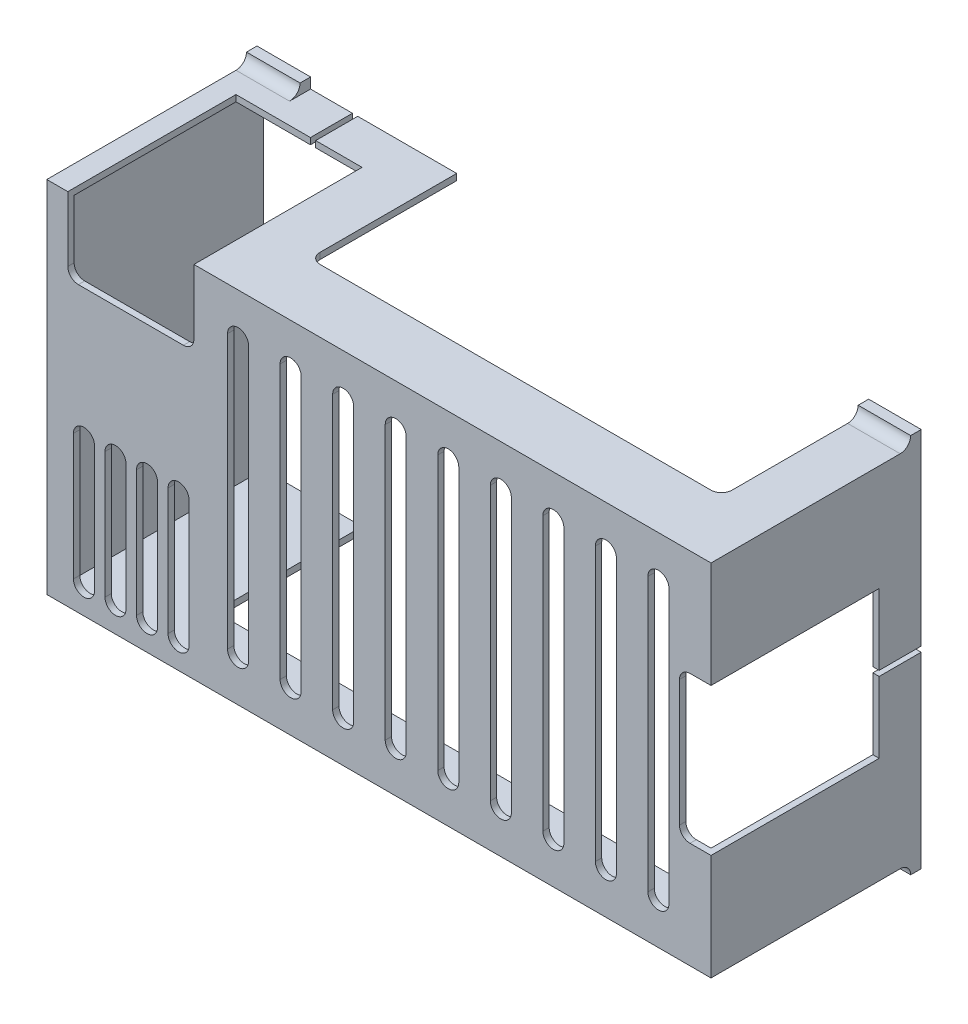
SolidWorks part; units mm, degrees
ref_plane "Front" through (0, 0, 0) normal (0, 0, 1) x (1, 0, 0)
ref_plane "Top" through (0, 0, 0) normal (0, 1, 0) x (1, 0, 0)
ref_plane "Right" through (0, 0, 0) normal (1, 0, 0) x (0, 0, -1)
sketch "Эскиз1" plane through (0, 0, 0) normal (0, 0, 1) x (1, 0, 0)
  line L1 (-62, 33) -> (62, 33)
  line L2 (-62, 33) -> (-62, -33)
  line L3 (-62, -33) -> (62, -33)
  line L4 (62, 33) -> (62, -33)
  line L5 (-62, 33) -> (62, -33) construction
  line L6 (-62, -33) -> (62, 33) construction
  point P0 (0, 0)
  dimension "D1" = 124
  dimension "D2" = 66
extrude "Вытянуть-Тонкостенный1" add sketch "Эскиз1" along normal blind 40 thin thin type one direction wall 1.2
sketch "Эскиз2" plane through (0, 0, 40) normal (0, 0, 1) x (1, 0, 0)
  line L1 (-63.2, 34.2) -> (63.2, 34.2)
  line L2 (-63.2, 34.2) -> (-63.2, -34.2)
  line L3 (-63.2, -34.2) -> (63.2, -34.2)
  line L4 (63.2, 34.2) -> (63.2, -34.2)
extrude "Бобышка-Вытянуть1" add sketch "Эскиз2" against normal blind 1.2
sketch "Эскиз3" plane through (0, 0, 40) normal (0, 0, 1) x (1, 0, 0)
  line L0 (63.2, -34.2) -> (63.2, 34.2) construction
  line L1 (59.2, -14) -> (69.2, -14)
  line L2 (57.2, -12) -> (57.2, 12)
  line L3 (59.2, 14) -> (69.2, 14)
  line L4 (69.2, -14) -> (69.2, 14)
  line L5 (57.2, -14) -> (69.2, 14) construction
  line L6 (57.2, 14) -> (69.2, -14) construction
  arc A0 (59.2, -14) -> (57.2, -12) centre (59.2, -12) cw
  arc A1 (57.2, 12) -> (59.2, 14) centre (59.2, 12) cw
  point P0 (63.2, 0)
  dimension "D3" = 2
  dimension "D1" = 12
  dimension "D2" = 28
extrude "Вырез-Вытянуть1" cut sketch "Эскиз3" against normal blind 32
sketch "Эскиз4" plane through (0, 0, 40) normal (0, 0, 1) x (1, 0, 0)
  line L0 (57.2, 0) -> (-63.2, 0) construction
  line L1 (57.2, 12) -> (57.2, -12) construction
  line L2 (-63.2, 34.2) -> (-63.2, -34.2) construction
  line L3 (53.2, -26) -> (53.2, 26) construction
  line L4 (51.2, -26) -> (51.2, 26)
  line L5 (55.2, -26) -> (55.2, 26)
  line L6 (63.2, 14) -> (63.2, -14) construction
  line L7 (43.2, -26) -> (43.2, 26) construction
  line L8 (41.2, -26) -> (41.2, 26)
  line L9 (45.2, -26) -> (45.2, 26)
  line L10 (33.2, -26) -> (33.2, 26) construction
  line L11 (31.2, -26) -> (31.2, 26)
  line L12 (35.2, -26) -> (35.2, 26)
  line L13 (23.2, -26) -> (23.2, 26) construction
  line L14 (21.2, -26) -> (21.2, 26)
  line L15 (25.2, -26) -> (25.2, 26)
  line L16 (13.2, -26) -> (13.2, 26) construction
  line L17 (11.2, -26) -> (11.2, 26)
  line L18 (15.2, -26) -> (15.2, 26)
  line L19 (3.2, -26) -> (3.2, 26) construction
  line L20 (1.2, -26) -> (1.2, 26)
  line L21 (5.2, -26) -> (5.2, 26)
  line L22 (-6.8, -26) -> (-6.8, 26) construction
  line L23 (-8.8, -26) -> (-8.8, 26)
  line L24 (-4.8, -26) -> (-4.8, 26)
  line L25 (-16.8, -26) -> (-16.8, 26) construction
  line L26 (-18.8, -26) -> (-18.8, 26)
  line L27 (-14.8, -26) -> (-14.8, 26)
  line L28 (-26.8, -26) -> (-26.8, 26) construction
  line L29 (-28.8, -26) -> (-28.8, 26)
  line L30 (-24.8, -26) -> (-24.8, 26)
  line L31 (-32.5505, 0) -> (-32.5505, -34.2) construction
  line L34 (-63.2, -34.2) -> (63.2, -34.2) construction
  line L35 (-32.5505, -17.1) -> (-63.2, -17.1) construction
  line L36 (-38.1278, -29.1) -> (-38.1278, -5.1) construction
  line L37 (-40.1278, -29.1) -> (-40.1278, -5.1)
  line L38 (-36.1278, -29.1) -> (-36.1278, -5.1)
  line L39 (-44.1278, -29.1) -> (-44.1278, -5.1) construction
  line L40 (-46.1278, -29.1) -> (-46.1278, -5.1)
  line L41 (-42.1278, -29.1) -> (-42.1278, -5.1)
  line L42 (-50.1278, -29.1) -> (-50.1278, -5.1) construction
  line L43 (-52.1278, -29.1) -> (-52.1278, -5.1)
  line L44 (-48.1278, -29.1) -> (-48.1278, -5.1)
  line L45 (-56.1278, -29.1) -> (-56.1278, -5.1) construction
  line L46 (-58.1278, -29.1) -> (-58.1278, -5.1)
  line L47 (-54.1278, -29.1) -> (-54.1278, -5.1)
  arc A0 (51.2, -26) -> (55.2, -26) centre (53.2, -26) ccw
  arc A1 (55.2, 26) -> (51.2, 26) centre (53.2, 26) ccw
  arc A2 (41.2, -26) -> (45.2, -26) centre (43.2, -26) ccw
  arc A3 (45.2, 26) -> (41.2, 26) centre (43.2, 26) ccw
  arc A4 (31.2, -26) -> (35.2, -26) centre (33.2, -26) ccw
  arc A5 (35.2, 26) -> (31.2, 26) centre (33.2, 26) ccw
  arc A6 (21.2, -26) -> (25.2, -26) centre (23.2, -26) ccw
  arc A7 (25.2, 26) -> (21.2, 26) centre (23.2, 26) ccw
  arc A8 (11.2, -26) -> (15.2, -26) centre (13.2, -26) ccw
  arc A9 (15.2, 26) -> (11.2, 26) centre (13.2, 26) ccw
  arc A10 (1.2, -26) -> (5.2, -26) centre (3.2, -26) ccw
  arc A11 (5.2, 26) -> (1.2, 26) centre (3.2, 26) ccw
  arc A12 (-8.8, -26) -> (-4.8, -26) centre (-6.8, -26) ccw
  arc A13 (-4.8, 26) -> (-8.8, 26) centre (-6.8, 26) ccw
  arc A14 (-18.8, -26) -> (-14.8, -26) centre (-16.8, -26) ccw
  arc A15 (-14.8, 26) -> (-18.8, 26) centre (-16.8, 26) ccw
  arc A16 (-28.8, -26) -> (-24.8, -26) centre (-26.8, -26) ccw
  arc A17 (-24.8, 26) -> (-28.8, 26) centre (-26.8, 26) ccw
  arc A20 (-40.1278, -29.1) -> (-36.1278, -29.1) centre (-38.1278, -29.1) ccw
  arc A21 (-36.1278, -5.1) -> (-40.1278, -5.1) centre (-38.1278, -5.1) ccw
  arc A22 (-46.1278, -29.1) -> (-42.1278, -29.1) centre (-44.1278, -29.1) ccw
  arc A23 (-42.1278, -5.1) -> (-46.1278, -5.1) centre (-44.1278, -5.1) ccw
  arc A24 (-52.1278, -29.1) -> (-48.1278, -29.1) centre (-50.1278, -29.1) ccw
  arc A25 (-48.1278, -5.1) -> (-52.1278, -5.1) centre (-50.1278, -5.1) ccw
  arc A26 (-58.1278, -29.1) -> (-54.1278, -29.1) centre (-56.1278, -29.1) ccw
  arc A27 (-54.1278, -5.1) -> (-58.1278, -5.1) centre (-56.1278, -5.1) ccw
  point P8 (53.2, 0)
  point P19 (43.2, 0)
  point P26 (33.2, 0)
  point P33 (23.2, 0)
  point P40 (13.2, 0)
  point P47 (3.2, 0)
  point P54 (-6.8, 0)
  point P61 (-16.8, 0)
  point P68 (-26.8, 0)
  point P79 (-38.1278, -17.1)
  point P88 (-44.1278, -17.1)
  point P95 (-50.1278, -17.1)
  point P102 (-56.1278, -17.1)
  dimension "D1" = 10
  dimension "D3" = 4
  dimension "D2" = 9
extrude "Вырез-Вытянуть2" cut sketch "Эскиз4" against normal up to next
sketch "Эскиз5" plane through (0, 0, 40) normal (0, 0, 1) x (1, 0, 0)
  line L0 (63.2, 34.2) -> (-63.2, 34.2) construction
  line L1 (-59.2, 48.5215) -> (-35.2, 48.5215)
  line L2 (-59.2, 48.5215) -> (-59.2, 21.8785)
  line L3 (-57.2, 19.8785) -> (-37.2, 19.8785)
  line L4 (-35.2, 48.5215) -> (-35.2, 21.8785)
  line L5 (-59.2, 48.5215) -> (-35.2, 19.8785) construction
  line L6 (-59.2, 19.8785) -> (-35.2, 48.5215) construction
  line L7 (-63.2, 34.2) -> (-63.2, -34.2) construction
  arc A0 (-37.2, 19.8785) -> (-35.2, 21.8785) centre (-37.2, 21.8785) ccw
  arc A1 (-59.2, 21.8785) -> (-57.2, 19.8785) centre (-57.2, 21.8785) ccw
  point P0 (-47.2, 34.2)
  dimension "D3" = 2
  dimension "D1" = 24
  dimension "D2" = 4
extrude "Вырез-Вытянуть3" cut sketch "Эскиз5" against normal blind 32
sketch "Эскиз6" plane through (0, -34.2, 0) normal (0, -1, 0) x (1, 0, 0)
  line L0 (-63.2, 0) -> (63.2, 0) construction
  line L1 (53.2, 0) -> (-43.2, 0)
  line L2 (53.2, 0) -> (53.2, 26)
  line L3 (51.2, 28) -> (-41.2, 28)
  line L4 (-43.2, 0) -> (-43.2, 26)
  line L5 (63.2, 40) -> (63.2, 0) construction
  line L6 (-63.2, 40) -> (-63.2, 0) construction
  arc A0 (53.2, 26) -> (51.2, 28) centre (51.2, 26) ccw
  arc A1 (-41.2, 28) -> (-43.2, 26) centre (-41.2, 26) ccw
  point P10 (-43.2, 28)
  dimension "D2" = 2
  dimension "D1" = 28
  dimension "D3" = 10
  dimension "D4" = 20
extrude "Вырез-Вытянуть4" cut sketch "Эскиз6" against normal up to next
sketch "Эскиз7" plane through (0, 34.2, 0) normal (0, 1, 0) x (1, 0, 0)
  line L0 (63.2, 0) -> (-63.2, 0) construction
  line L1 (53.2, 0) -> (-25.2, 0)
  line L2 (53.2, 0) -> (53.2, -26)
  line L3 (51.2, -28) -> (-23.2, -28)
  line L4 (-25.2, 0) -> (-25.2, -26)
  line L5 (63.2, -40) -> (63.2, 0) construction
  line L6 (-35.2, -8) -> (-35.2, -40) construction
  arc A0 (53.2, -26) -> (51.2, -28) centre (51.2, -26) cw
  arc A1 (-23.2, -28) -> (-25.2, -26) centre (-23.2, -26) cw
  point P14 (-25.2, -28)
  dimension "D4" = 2
  dimension "D1" = 28
  dimension "D2" = 10
  dimension "D3" = 10
extrude "Вырез-Вытянуть5" cut sketch "Эскиз7" against normal up to next
sketch "Эскиз8" plane through (0, 0, 0) normal (0, 0, -1) x (-1, 0, 0)
  line L1 (-63.2, 34.2) -> (-53.2, 34.2)
  line L2 (-63.2, 34.2) -> (-63.2, 36.2)
  line L3 (-63.2, 36.2) -> (-53.2, 36.2)
  line L4 (-53.2, 34.2) -> (-53.2, 36.2)
  line L5 (-63.2, -34.2) -> (-53.2, -34.2)
  line L6 (-63.2, -34.2) -> (-63.2, -36.2)
  line L7 (-63.2, -36.2) -> (-53.2, -36.2)
  line L8 (-53.2, -34.2) -> (-53.2, -36.2)
  line L9 (63.2, 34.2) -> (53.0055, 34.2)
  line L10 (63.2, 34.2) -> (63.2, 36.2)
  line L11 (63.2, 36.2) -> (53.0055, 36.2)
  line L12 (53.0055, 34.2) -> (53.0055, 36.2)
  line L13 (63.2, -34.2) -> (53.0055, -34.2)
  line L14 (63.2, -34.2) -> (63.2, -36.2)
  line L15 (63.2, -36.2) -> (53.0055, -36.2)
  line L16 (53.0055, -34.2) -> (53.0055, -36.2)
  dimension "D1" = 2
  dimension "D2" = 2
extrude "Бобышка-Вытянуть2" add sketch "Эскиз8" against normal blind 2
fillet "Скругление1" radius 2 4 edges at (-58.1028, -34.2, 2) (58.2, -34.2, 2) (58.2, 34.2, 2) (-58.1028, 34.2, 2)
sketch "Эскиз9" plane through (63.2, 0, 0) normal (1, 0, 0) x (0, 0, -1)
  line L0 (-8, 14) -> (-8, -14) construction
  line L1 (8, -0.5) -> (-8, -0.5)
  line L2 (8, -0.5) -> (8, 0.5)
  line L3 (8, 0.5) -> (-8, 0.5)
  line L4 (-8, -0.5) -> (-8, 0.5)
  line L5 (8, -0.5) -> (-8, 0.5) construction
  line L6 (8, 0.5) -> (-8, -0.5) construction
  point P0 (0, 0)
  dimension "D1" = 1
extrude "Вырез-Вытянуть6" cut sketch "Эскиз9" against normal up to next
sketch "Эскиз10" plane through (0, 34.2, 0) normal (0, 1, 0) x (1, 0, 0)
  line L0 (-25.2, 0) -> (-53.0055, 0) construction
  line L1 (-45.0307, 8) -> (-44.0307, 8)
  line L2 (-45.0307, 8) -> (-45.0307, -8)
  line L3 (-45.0307, -8) -> (-44.0307, -8)
  line L4 (-44.0307, 8) -> (-44.0307, -8)
  line L5 (-45.0307, 8) -> (-44.0307, -8) construction
  line L6 (-45.0307, -8) -> (-44.0307, 8) construction
  line L7 (-35.2, -8) -> (-59.2, -8) construction
  point P0 (-44.5307, 0)
  dimension "D1" = 1
extrude "Вырез-Вытянуть7" cut sketch "Эскиз10" against normal up to next
